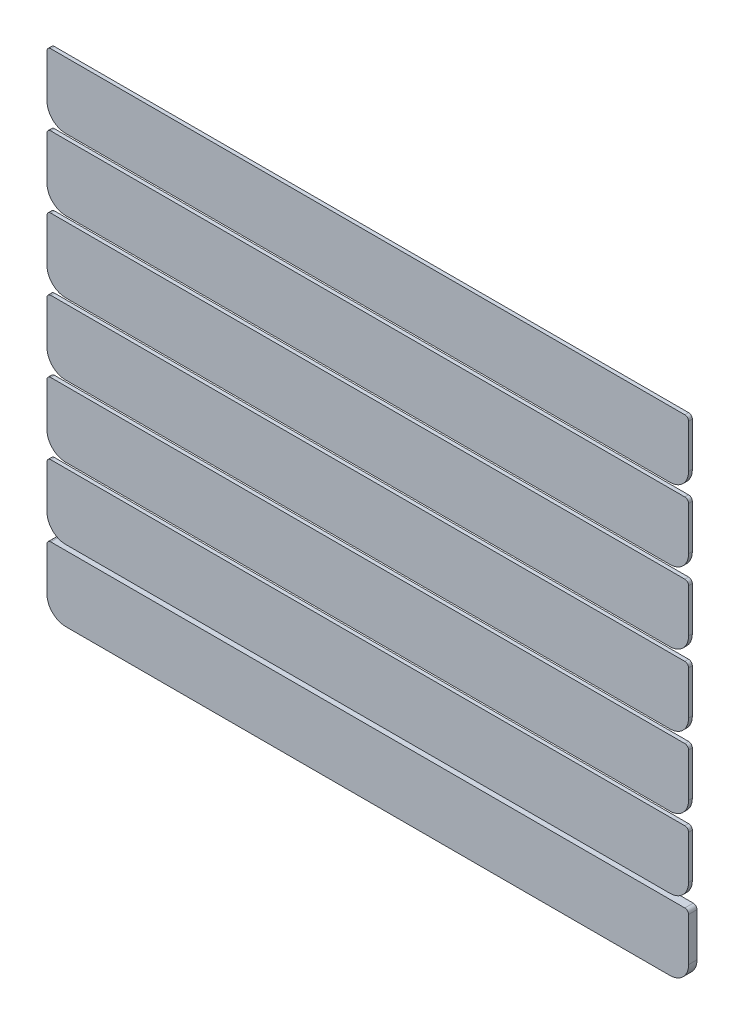
SolidWorks part; units mm, degrees
ref_plane "Front Plane" through (0, 0, 0) normal (0, 0, 1) x (1, 0, 0)
ref_plane "Top Plane" through (0, 0, 0) normal (0, 1, 0) x (1, 0, 0)
ref_plane "Right Plane" through (0, 0, 0) normal (1, 0, 0) x (0, 0, -1)
sketch "Sketch1" plane through (0, 0, 0) normal (0, 0, 1) x (1, 0, 0)
  line L1 (-217.4875, -22.352) -> (217.4875, -22.352)
  line L2 (-217.4875, -22.352) -> (-217.4875, 22.352)
  line L3 (-217.4875, 22.352) -> (217.4875, 22.352)
  line L4 (217.4875, -22.352) -> (217.4875, 22.352)
  line L5 (-217.4875, -22.352) -> (217.4875, 22.352) construction
  line L6 (-217.4875, 22.352) -> (217.4875, -22.352) construction
  point P0 (0, 0)
  dimension "D1" = 44.704
  dimension "D2" = 434.975
extrude "Boss-Extrude1" add sketch "Sketch1" along normal blind 3.175
fillet "Fillet1" radius 12.7 2 edges at (217.4875, -22.352, 1.5875) (-217.4875, -22.352, 1.5875)
hole_wizard "#1 (0.228) Diameter Hole1" positions "Sketch2" profile "Sketch3" hole size "#1" standard "ANSI Inch" end condition through all
sketch "Sketch2" plane through (0, 0, 3.175) normal (0, 0, 1) x (1, 0, 0)
  line L0 (-217.4875, 12.7) -> (217.4875, 12.7) construction
  line L1 (-217.4875, 22.352) -> (-217.4875, -9.652) construction
  line L2 (217.4875, -9.652) -> (217.4875, 22.352) construction
  line L3 (217.4875, 22.352) -> (-217.4875, 22.352) construction
  point P10 (-166.6875, 12.7)
  point P12 (166.6875, 12.7)
  dimension "D1" = 9.652
  dimension "D2" = 333.375
  dimension "D3" = 50.8
sketch "Sketch3" plane through (166.6875, 12.7, 3.175) normal (1, 0, 0) x (0, -1, 0)
  line L0 (0, 0) -> (0, 3.175)
  line L1 (0, 3.175) -> (2.8956, 3.175)
  line L2 (2.8956, 3.175) -> (2.8956, 0)
  line L5 (2.8956, 0) -> (0, 0)
  line L11 (0, -6.35) -> (0, 107.95) construction
  dimension "Thru Hole Dia." = 5.7912
  dimension "Thru Hole Depth" = 3.175
fillet "Fillet2" radius 2.54 2 edges at (217.4875, 22.352, 1.5875) (-217.4875, 22.352, 1.5875)
sketch "Sketch4" plane through (0, 0, 3.175) normal (0, 0, 1) x (1, 0, 0)
  line L4 (217.4875, 38.608) -> (217.4875, 68.072)
  line L5 (214.9475, 70.612) -> (-214.9475, 70.612)
  line L6 (-217.4875, 68.072) -> (-217.4875, 38.608)
  line L7 (-204.7875, 25.908) -> (204.7875, 25.908)
  line L8 (217.4875, -9.652) -> (217.4875, 19.812)
  line L9 (214.9475, 22.352) -> (-214.9475, 22.352)
  line L10 (-217.4875, 19.812) -> (-217.4875, -9.652)
  line L11 (-204.7875, -22.352) -> (204.7875, -22.352)
  line L12 (217.4875, -9.652) -> (217.4875, 19.812)
  line L13 (214.9475, 22.352) -> (-214.9475, 22.352)
  line L14 (-217.4875, 19.812) -> (-217.4875, -9.652)
  line L15 (-204.7875, -22.352) -> (204.7875, -22.352)
  line L16 (217.4875, 86.868) -> (217.4875, 116.332)
  line L17 (214.9475, 118.872) -> (-214.9475, 118.872)
  line L18 (-217.4875, 116.332) -> (-217.4875, 86.868)
  line L19 (-204.7875, 74.168) -> (204.7875, 74.168)
  line L20 (217.4875, 135.128) -> (217.4875, 164.592)
  line L21 (214.9475, 167.132) -> (-214.9475, 167.132)
  line L22 (-217.4875, 164.592) -> (-217.4875, 135.128)
  line L23 (-204.7875, 122.428) -> (204.7875, 122.428)
  line L24 (217.4875, 183.388) -> (217.4875, 212.852)
  line L25 (214.9475, 215.392) -> (-214.9475, 215.392)
  line L26 (-217.4875, 212.852) -> (-217.4875, 183.388)
  line L27 (-204.7875, 170.688) -> (204.7875, 170.688)
  line L28 (217.4875, 231.648) -> (217.4875, 261.112)
  line L29 (214.9475, 263.652) -> (-214.9475, 263.652)
  line L30 (-217.4875, 261.112) -> (-217.4875, 231.648)
  line L31 (-204.7875, 218.948) -> (204.7875, 218.948)
  line L32 (217.4875, 279.908) -> (217.4875, 309.372)
  line L33 (214.9475, 311.912) -> (-214.9475, 311.912)
  line L34 (-217.4875, 309.372) -> (-217.4875, 279.908)
  line L35 (-204.7875, 267.208) -> (204.7875, 267.208)
  arc A4 (217.4875, 68.072) -> (214.9475, 70.612) centre (214.9475, 68.072) ccw
  arc A5 (-214.9475, 70.612) -> (-217.4875, 68.072) centre (-214.9475, 68.072) ccw
  arc A6 (-217.4875, 38.608) -> (-204.7875, 25.908) centre (-204.7875, 38.608) ccw
  arc A7 (204.7875, 25.908) -> (217.4875, 38.608) centre (204.7875, 38.608) ccw
  arc A9 (217.4875, 19.812) -> (214.9475, 22.352) centre (214.9475, 19.812) ccw
  arc A11 (-214.9475, 22.352) -> (-217.4875, 19.812) centre (-214.9475, 19.812) ccw
  arc A12 (-217.4875, -9.652) -> (-204.7875, -22.352) centre (-204.7875, -9.652) ccw
  arc A13 (204.7875, -22.352) -> (217.4875, -9.652) centre (204.7875, -9.652) ccw
  arc A14 (217.4875, 19.812) -> (214.9475, 22.352) centre (214.9475, 19.812) ccw
  arc A15 (-214.9475, 22.352) -> (-217.4875, 19.812) centre (-214.9475, 19.812) ccw
  arc A16 (-217.4875, -9.652) -> (-204.7875, -22.352) centre (-204.7875, -9.652) ccw
  arc A17 (204.7875, -22.352) -> (217.4875, -9.652) centre (204.7875, -9.652) ccw
  arc A18 (217.4875, 116.332) -> (214.9475, 118.872) centre (214.9475, 116.332) ccw
  arc A19 (-214.9475, 118.872) -> (-217.4875, 116.332) centre (-214.9475, 116.332) ccw
  arc A20 (-217.4875, 86.868) -> (-204.7875, 74.168) centre (-204.7875, 86.868) ccw
  arc A21 (204.7875, 74.168) -> (217.4875, 86.868) centre (204.7875, 86.868) ccw
  arc A22 (217.4875, 164.592) -> (214.9475, 167.132) centre (214.9475, 164.592) ccw
  arc A23 (-214.9475, 167.132) -> (-217.4875, 164.592) centre (-214.9475, 164.592) ccw
  arc A24 (-217.4875, 135.128) -> (-204.7875, 122.428) centre (-204.7875, 135.128) ccw
  arc A25 (204.7875, 122.428) -> (217.4875, 135.128) centre (204.7875, 135.128) ccw
  arc A26 (217.4875, 212.852) -> (214.9475, 215.392) centre (214.9475, 212.852) ccw
  arc A27 (-214.9475, 215.392) -> (-217.4875, 212.852) centre (-214.9475, 212.852) ccw
  arc A28 (-217.4875, 183.388) -> (-204.7875, 170.688) centre (-204.7875, 183.388) ccw
  arc A29 (204.7875, 170.688) -> (217.4875, 183.388) centre (204.7875, 183.388) ccw
  arc A30 (217.4875, 261.112) -> (214.9475, 263.652) centre (214.9475, 261.112) ccw
  arc A31 (-214.9475, 263.652) -> (-217.4875, 261.112) centre (-214.9475, 261.112) ccw
  arc A32 (-217.4875, 231.648) -> (-204.7875, 218.948) centre (-204.7875, 231.648) ccw
  arc A33 (204.7875, 218.948) -> (217.4875, 231.648) centre (204.7875, 231.648) ccw
  arc A34 (217.4875, 309.372) -> (214.9475, 311.912) centre (214.9475, 309.372) ccw
  arc A35 (-214.9475, 311.912) -> (-217.4875, 309.372) centre (-214.9475, 309.372) ccw
  arc A36 (-217.4875, 279.908) -> (-204.7875, 267.208) centre (-204.7875, 279.908) ccw
  arc A37 (204.7875, 267.208) -> (217.4875, 279.908) centre (204.7875, 279.908) ccw
  dimension "D1" = 0
  dimension "D2" = 7
extrude "Boss-Extrude2" add sketch "Sketch4" along normal blind 2.54
